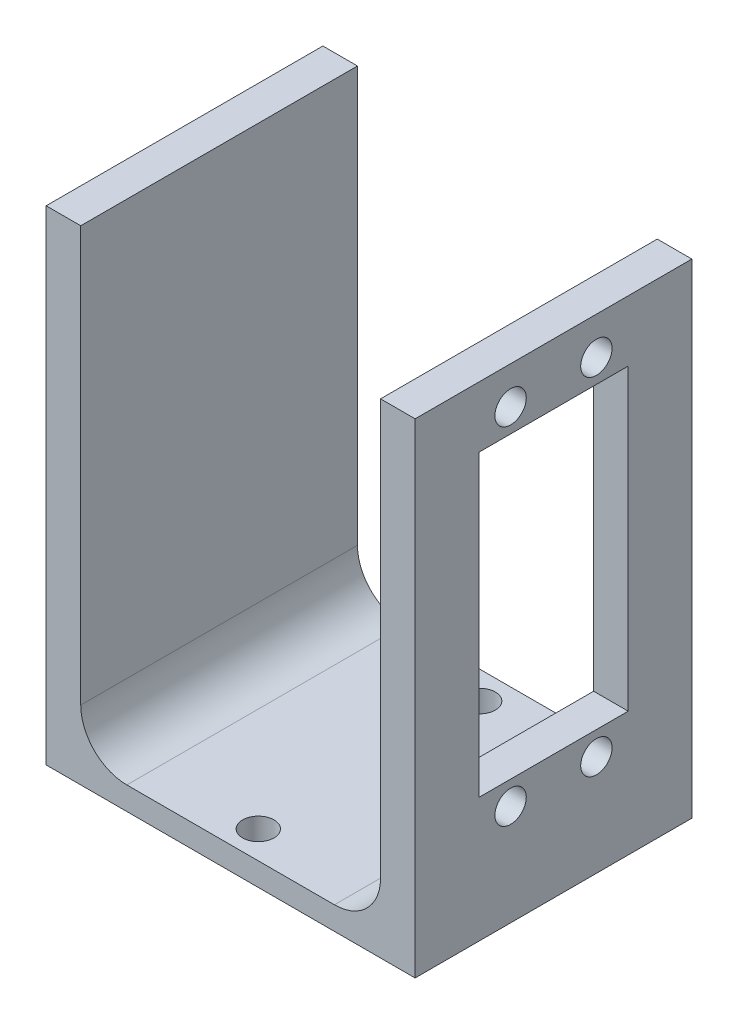
SolidWorks part; units mm, degrees
ref_plane "Front" through (0, 0, 0) normal (0, 0, 1) x (1, 0, 0)
ref_plane "Top" through (0, 0, 0) normal (0, 1, 0) x (1, 0, 0)
ref_plane "Right" through (0, 0, 0) normal (1, 0, 0) x (0, 0, -1)
sketch "Sketch1" plane through (0, 0, 0) normal (0, 1, 0) x (1, 0, 0)
  line L1 (0, 0) -> (50.8, 0)
  line L2 (0, 0) -> (0, 38.1)
  line L3 (0, 38.1) -> (50.8, 38.1)
  line L4 (50.8, 0) -> (50.8, 38.1)
  dimension "D1" = 38.1
  dimension "D2" = 50.8
extrude "Boss-Extrude1" add sketch "Sketch1" along normal blind 3.175
sketch "Sketch2" plane through (0, 3.175, 0) normal (0, 1, 0) x (1, 0, 0)
  line L0 (0, 0) -> (50.8, 0) construction
  line L1 (50.8, 38.1) -> (46.0375, 38.1)
  line L2 (50.8, 38.1) -> (50.8, 0)
  line L3 (50.8, 0) -> (46.0375, 0)
  line L4 (46.0375, 38.1) -> (46.0375, 0)
  line L5 (50.8, 38.1) -> (0, 38.1) construction
  line L6 (4.7625, 38.1) -> (0, 38.1)
  line L7 (4.7625, 38.1) -> (4.7625, 0)
  line L8 (4.7625, 0) -> (0, 0)
  line L9 (0, 38.1) -> (0, 0)
  dimension "D1" = 4.7625
extrude "Boss-Extrude2" add sketch "Sketch2" along normal blind 63.5
fillet "Fillet1" radius 6.35 2 edges at (4.7625, 3.175, -19.05) (46.0375, 3.175, -19.05)
sketch "Sketch3" plane through (50.8, 0, 0) normal (1, 0, 0) x (0, 0, -1)
  line L0 (0, 0) -> (38.1, 0) construction
  line L1 (38.1, 66.675) -> (38.1, 0) construction
  line L2 (0, 66.675) -> (38.1, 66.675) construction
  line L5 (8.763, 58.293) -> (29.337, 58.293)
  line L6 (8.763, 58.293) -> (8.763, 17.145)
  line L7 (8.763, 17.145) -> (29.337, 17.145)
  line L8 (29.337, 58.293) -> (29.337, 17.145)
  point P0 (19.05, 10.3505)
  point P3 (19.05, 0)
  point P8 (19.05, 65.0875)
  point P9 (19.05, 66.675)
  point P14 (19.05, 17.145)
  point P15 (29.337, 37.719)
  point P16 (28.8925, 37.719)
  line B0 (28.8925, 65.0875) -> (28.8925, 10.3505) construction
  line B1 (28.8925, 65.0875) -> (9.2075, 65.0875) construction
  line B2 (9.2075, 65.0875) -> (9.2075, 10.3505) construction
  circle B3 centre (24.9555, 61.5315) radius 2.159
  circle B4 centre (13.1445, 61.5315) radius 2.159
  circle B5 centre (13.1445, 13.9065) radius 2.159
  circle B6 centre (24.9555, 13.9065) radius 2.159
  dimension "D1" = 1.5875
  dimension "D2" = 41.148
  dimension "D3" = 20.574
sketch_block_instance "ServoMountingHoles-1"
sketch_block "ServoMountingHoles"
extrude "Cut-Extrude1" cut sketch "Sketch3" against normal up to next
sketch "Sketch4" plane through (0, 3.175, 0) normal (0, 1, 0) x (1, 0, 0)
  line L0 (25.4, 34.29) -> (25.4, 3.81) construction
  line L1 (11.1125, 19.05) -> (39.6875, 19.05) construction
  line L2 (11.1125, 38.1) -> (11.1125, 0) construction
  line L3 (39.6875, 0) -> (39.6875, 38.1) construction
  circle A0 centre (25.4, 34.29) radius 2.159
  circle A1 centre (25.4, 3.81) radius 2.159
  point P10 (25.4, 19.05)
  dimension "D1" = 30.48
  dimension "D2" = 4.318
extrude "Cut-Extrude2" cut sketch "Sketch4" against normal up to next
